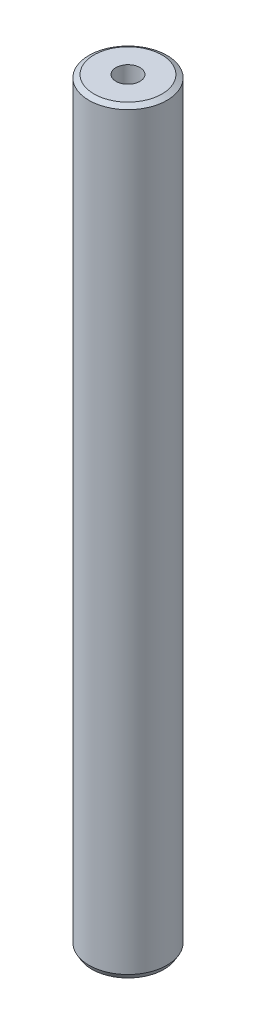
SolidWorks part; units mm, degrees
ref_plane "Front Plane" through (0, 0, 0) normal (0, 0, 1) x (1, 0, 0)
ref_plane "Top Plane" through (0, 0, 0) normal (0, 1, 0) x (1, 0, 0)
ref_plane "Right Plane" through (0, 0, 0) normal (1, 0, 0) x (0, 0, -1)
sketch "Sketch1" plane through (0, 0, 0) normal (0, 1, 0) x (1, 0, 0)
  circle A0 centre (0, 0) radius 20
  dimension "SHAFT_OD" = 40
extrude "Boss-Extrude1" add sketch "Sketch1" along normal blind 388.1583
sketch "Sketch2" plane through (0, 0, 0) normal (0, 1, 0) x (1, 0, 0)
  circle A0 centre (0, 0) radius 6.1505
  dimension "BORE_D" = 12.301
extrude "Cut-Extrude1" cut sketch "Sketch2" along normal through all
chamfer "Chamfer1" distance 1.5056 angle 60 2 edges at (0, 388.1583, 20) (0, 0, 20) first distance on face at (0, 388.1583, 20) first distance on face at (0, 0, 6.1505)
